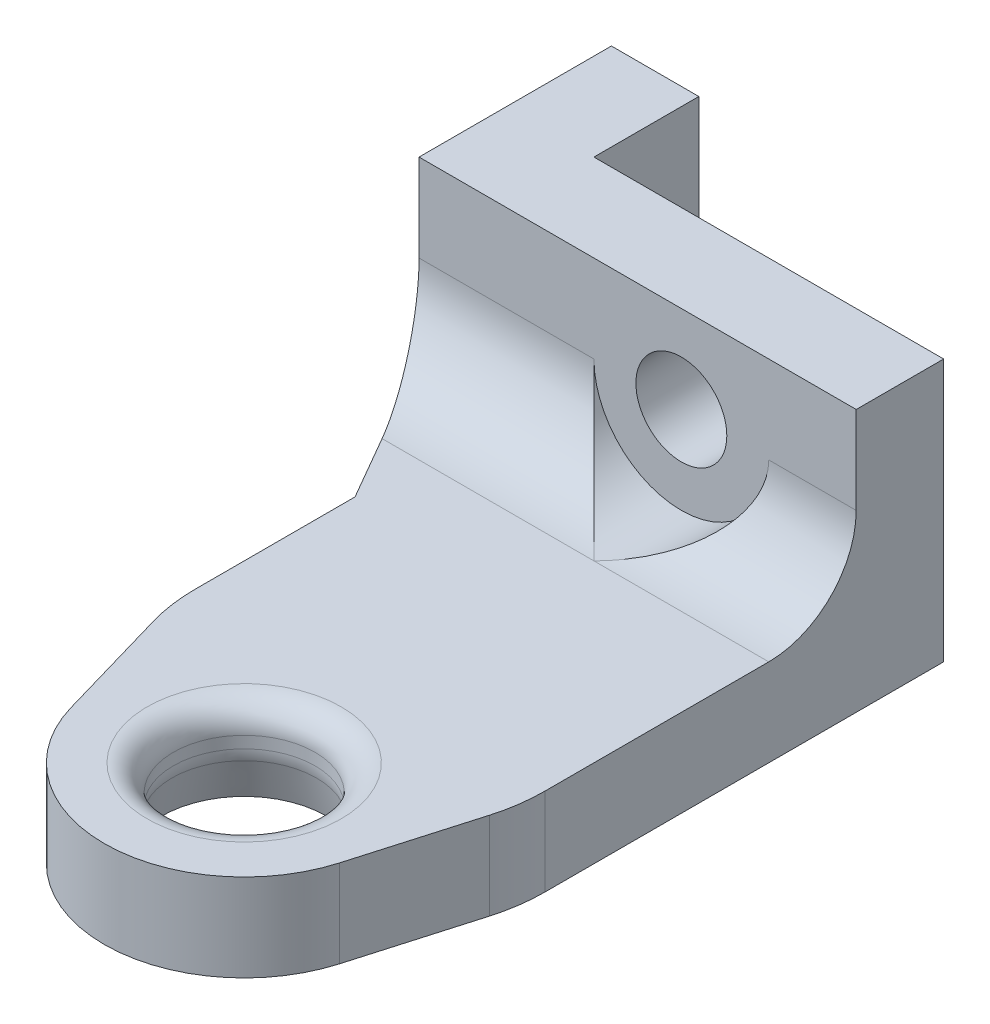
SolidWorks part; units mm, degrees
ref_plane "Front" through (0, 0, 0) normal (0, 0, 1) x (1, 0, 0)
ref_plane "Top" through (0, 0, 0) normal (0, 1, 0) x (1, 0, 0)
ref_plane "Right" through (0, 0, 0) normal (1, 0, 0) x (0, 0, -1)
sketch "Sketch1" plane through (0, 0, 0) normal (0, 1, 0) x (1, 0, 0)
  line L0 (0, 40) -> (0, 0) construction
  line L1 (-10, 30) -> (10, 30)
  line L2 (-10, 30) -> (-10, 50)
  line L3 (-10, 50) -> (10, 50)
  line L4 (10, 30) -> (10, 50)
  line L5 (-10, 30) -> (10, 50) construction
  line L6 (-10, 50) -> (10, 30) construction
  circle A0 centre (0, 0) radius 4
  point P3 (0, 40)
  dimension "D1" = 20
  dimension "D3" = 8
  dimension "D2" = 30
sketch "Sketch2" plane through (0, 0, 0) normal (0, 1, 0) x (1, 0, 0)
  line L0 (-7.6846, -2.2241) -> (-10, 5.7759)
  line L1 (-10, 5.7759) -> (-10, 30)
  line L2 (-10, 30) -> (10, 30) construction
  line L4 (0, 40) -> (0, 0) construction
  line L5 (0, 40) -> (0, 0) construction
  line L6 (10, 5.7759) -> (10, 30)
  line L7 (7.6846, -2.2241) -> (10, 5.7759)
  line L8 (-10, 30) -> (10, 30)
  circle A0 centre (0, 0) radius 8 construction
  circle A1 centre (0, 0) radius 4 construction
  arc A2 (7.6846, -2.2241) -> (-7.6846, -2.2241) centre (0, 0) cw
  circle A3 centre (0, 0) radius 4.05
  dimension "D1" = 4
  dimension "D2" = 8
  dimension "D3" = 8.1
extrude "Boss-Extrude1" add sketch "Sketch2" along normal blind 5
fillet "Fillet1" radius 10 2 edges at (10, 2.5, -5.7759) (-10, 2.5, -5.7759)
sketch "Sketch3" plane through (0, 0, -30) normal (0, 0, -1) x (-1, 0, 0)
  line L0 (10, 5) -> (10, 0) construction
  line L1 (-10, 0) -> (10, 0)
  line L2 (-10, 0) -> (-10, 15)
  line L3 (-10, 15) -> (10, 15)
  line L4 (10, 0) -> (10, 15)
  line L5 (-10, 5) -> (10, 5) construction
  dimension "D1" = 10
extrude "Boss-Extrude2" add sketch "Sketch3" against normal blind 5
sketch "Sketch6" plane through (0, 0, -25) normal (0, 0, 1) x (1, 0, 0)
  line L0 (0, 15) -> (0, 10) construction
  line L1 (-10, 15) -> (10, 15) construction
  line L2 (0, 10) -> (0, 5) construction
  line L3 (7.6846, 5) -> (-7.6846, 5) construction
  circle A0 centre (0, 10) radius 2.6
  dimension "D1" = 5.2
extrude "Cut-Extrude1" cut sketch "Sketch6" against normal through all
sketch "Sketch4" plane through (-10, 0, 0) normal (-1, 0, 0) x (0, 0, 1)
  line L0 (-25, 15) -> (-30, 15) construction
  line L1 (-25, 15) -> (-36, 15)
  line L2 (-25, 15) -> (-25, 0)
  line L3 (-25, 0) -> (-36, 0)
  line L4 (-36, 15) -> (-36, 0)
  line L5 (-25, 5) -> (-25, 15) construction
  line L6 (-30, 0) -> (-7.1939, 0) construction
  line L7 (-30, 15) -> (-30, 0) construction
  dimension "D1" = 6
extrude "Boss-Extrude3" add sketch "Sketch4" along normal blind 5
chamfer "Chamfer1" distance 5 angle 60 1 edges at (-10, 2.5, -25) first distance on face at (2.6, 10, -25)
fillet "Fillet2" radius 5 1 edges at (-2.5, 5, -25)
sketch "Sketch7" plane through (0, 0, -25) normal (0, 0, 1) x (1, 0, 0)
  circle A0 centre (0, 10) radius 5
  dimension "D1" = 10
extrude "Cut-Extrude3" cut sketch "Sketch7" along normal through all
chamfer "Chamfer2" distance 2.5 angle 15 1 edges at (0, 0, 4.05) first distance on face at (0, 5, 4.05)
fillet "Fillet3" radius 1.5 1 edges at (0, 5, 4.05)
fillet "Fillet4" radius 2.5 1 edges at (0, 2.5, -4.05)
mirror "Mirror1" [suppressed] of bodies 107
delete or keep bodies "Body-Delete/Keep 1" [suppressed] type delete bodies bodies 107
sketch "Sketch8" [suppressed] plane through (0, 0, 0) normal (0, -1, 0) x (1, 0, 0)
  line L0 (23, -30) -> (23, -5) construction
  line L1 (10, -30) -> (30, -30) construction
  line L2 (30, -16.3397) -> (30, -7.1939) construction
  text T0 "RLR-02" font "Century Gothic" height in points 20
  dimension "D1" = 7
  dimension "D2" = 25
extrude "Cut-Extrude4" [suppressed] cut sketch "Sketch8" against normal blind 0.4
sketch "Sketch9" plane through (0, 0, 0) normal (0, -1, 0) x (1, 0, 0)
  line L0 (3, -30) -> (3, -5) construction
  line L1 (10, -30) -> (-10, -30) construction
  line L2 (10, -7.1939) -> (10, -30) construction
  text T0 "LLR-03" font "Century Gothic" height in points 20
  dimension "D1" = 25
  dimension "D2" = 7
extrude "Cut-Extrude5" cut sketch "Sketch9" against normal blind 0.4
